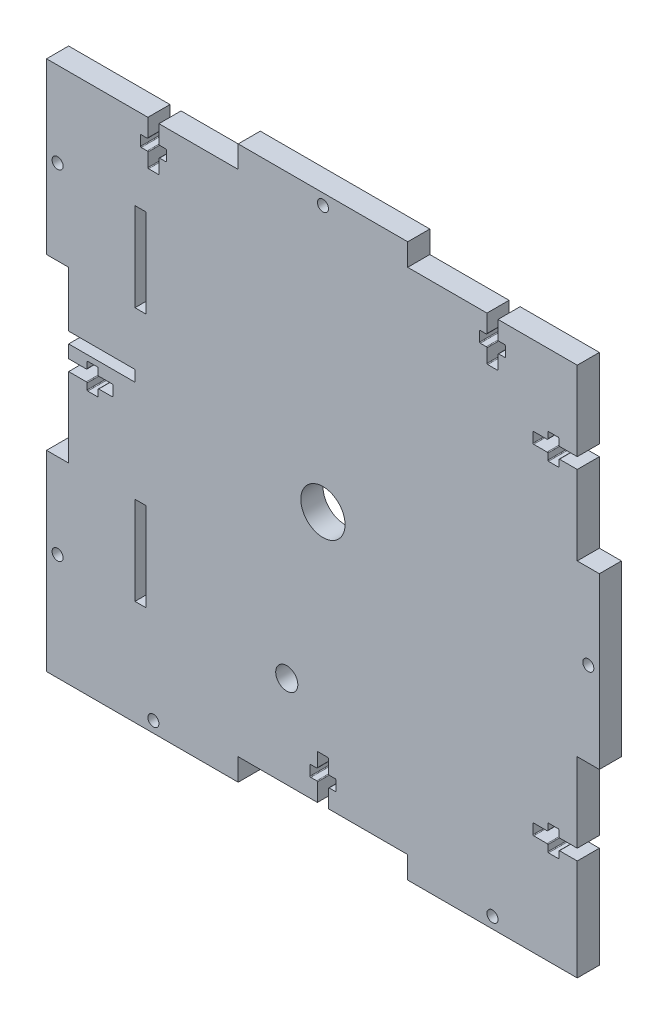
SolidWorks part; units mm, degrees
ref_plane "Front Plane" through (0, 0, 0) normal (0, 0, 1) x (1, 0, 0)
ref_plane "Top Plane" through (0, 0, 0) normal (0, 1, 0) x (1, 0, 0)
ref_plane "Right Plane" through (0, 0, 0) normal (1, 0, 0) x (0, 0, -1)
sketch "Sketch1" plane through (0, 0, 0) normal (0, 0, 1) x (1, 0, 0)
  line L0 (-69, 69) -> (-23, 69)
  line L5 (-75, -75) -> (75, -75) construction
  line L6 (-75, -75) -> (-75, 75) construction
  line L7 (-75, 75) -> (75, 75) construction
  line L8 (75, -75) -> (75, 75) construction
  line L9 (75, 23) -> (69, 23)
  line L10 (69, -23) -> (75, -23)
  line L11 (-69, -69) -> (69, -69) construction
  line L12 (-69, -69) -> (-69, 69) construction
  line L13 (-69, 69) -> (69, 69) construction
  line L14 (69, -69) -> (69, 69) construction
  line L15 (-69, -69) -> (69, 69) construction
  line L16 (69, -69) -> (69, -23)
  line L17 (-23, 69) -> (-23, 75)
  line L18 (-23, 75) -> (23, 75)
  line L19 (23, 75) -> (23, 69)
  line L20 (23, 69) -> (69, 69)
  line L21 (75, -23) -> (75, 23)
  line L22 (69, 23) -> (69, 69)
  line L23 (-75, 23) -> (-69, 23)
  line L24 (-69, 69) -> (-75, 69)
  line L25 (-75, 69) -> (-75, 23)
  line L26 (69, -69) -> (69, -75)
  line L27 (69, -75) -> (23, -75)
  line L28 (23, -75) -> (23, -69)
  line L29 (23, -69) -> (-23, -69)
  line L30 (-23, -69) -> (-23, -75)
  line L31 (-23, -75) -> (-69, -75)
  line L32 (-69, -75) -> (-69, -69) construction
  line L33 (-69, 23) -> (-69, -23)
  line L34 (-69, -23) -> (-75, -23)
  line L35 (-75, -23) -> (-75, -69)
  line L36 (-75, -69) -> (-69, -69) construction
  line L37 (-46, 69) -> (-46, -75) construction
  line L38 (-69, 69) -> (69, -69) construction
  line L39 (-75, -75) -> (-69, -75)
  line L40 (-75, -75) -> (-75, -69)
  point P0 (0, 0)
  point P6 (-7, -7)
  point P26 (0, -75)
  point P27 (-75, 0)
  dimension "D1" = 150
  dimension "D2" = 150
  dimension "D5" = 46
  dimension "D3" = 6
  dimension "D6" = 6
  dimension "D7" = 6
extrude "Box Side" add sketch "Sketch1" along normal blind 6
sketch "Sketch2" plane through (0, 0, 6) normal (0, 0, 1) x (1, 0, 0)
  line L0 (23, 72) -> (-23, 72) construction
  line L1 (23, 75) -> (23, 69) construction
  line L2 (-23, 69) -> (-23, 75) construction
  line L3 (-46, 69) -> (-46, -75) construction
  line L5 (0, 75) -> (0, 69) construction
  line L6 (-23, 75) -> (23, 75) construction
  line L7 (-69, 69) -> (69, 69) construction
  line L16 (-46, 69) -> (-46, -75) construction
  line L21 (0, -69) -> (0, 69) construction
  line L35 (-69, 69) -> (-23, 69) construction
  line L36 (-44.5, 69) -> (-44.5, 64.2)
  line L37 (-44.3, 64) -> (-42.7, 64)
  line L38 (-42.5, 63.8) -> (-42.5, 61.2)
  line L39 (-42.7, 61) -> (-44.3, 61)
  line L40 (-44.5, 60.8) -> (-44.5, 57.2)
  line L46 (-44.7, 57) -> (-47.3, 57)
  line L48 (-44.5, 69) -> (-47.5, 69)
  line L51 (-47.5, 60.8) -> (-47.5, 57.2)
  line L52 (-49.3, 61) -> (-47.7, 61)
  line L53 (-49.5, 63.8) -> (-49.5, 61.2)
  line L54 (-47.7, 64) -> (-49.3, 64)
  line L55 (-47.5, 69) -> (-47.5, 64.2)
  line L56 (47.5, 69) -> (47.5, 64.2)
  line L57 (47.7, 64) -> (49.3, 64)
  line L58 (49.5, 63.8) -> (49.5, 61.2)
  line L59 (49.3, 61) -> (47.7, 61)
  line L60 (47.5, 60.8) -> (47.5, 57.2)
  line L61 (44.5, 69) -> (47.5, 69)
  line L62 (44.7, 57) -> (47.3, 57)
  line L63 (44.5, 60.8) -> (44.5, 57.2)
  line L64 (42.7, 61) -> (44.3, 61)
  line L65 (42.5, 63.8) -> (42.5, 61.2)
  line L66 (44.3, 64) -> (42.7, 64)
  line L67 (44.5, 69) -> (44.5, 64.2)
  line L68 (-69, -69) -> (69, 69) construction
  line L69 (-69, -69) -> (69, 69) construction
  line L70 (75, 0) -> (69, 0) construction
  line L71 (72, 23) -> (72, -23) construction
  line L72 (69, 44.5) -> (64.2, 44.5)
  line L73 (64, 44.3) -> (64, 42.7)
  line L74 (63.8, 42.5) -> (61.2, 42.5)
  line L75 (61, 42.7) -> (61, 44.3)
  line L76 (60.8, 44.5) -> (57.2, 44.5)
  line L77 (57, 44.7) -> (57, 47.3)
  line L78 (69, 44.5) -> (69, 47.5)
  line L79 (60.8, 47.5) -> (57.2, 47.5)
  line L80 (61, 49.3) -> (61, 47.7)
  line L81 (63.8, 49.5) -> (61.2, 49.5)
  line L82 (64, 47.7) -> (64, 49.3)
  line L83 (69, 47.5) -> (64.2, 47.5)
  line L84 (69, -47.5) -> (64.2, -47.5)
  line L85 (64, -47.7) -> (64, -49.3)
  line L86 (63.8, -49.5) -> (61.2, -49.5)
  line L87 (61, -49.3) -> (61, -47.7)
  line L88 (60.8, -47.5) -> (57.2, -47.5)
  line L89 (69, -44.5) -> (69, -47.5)
  line L90 (57, -44.7) -> (57, -47.3)
  line L91 (60.8, -44.5) -> (57.2, -44.5)
  line L92 (61, -42.7) -> (61, -44.3)
  line L93 (63.8, -42.5) -> (61.2, -42.5)
  line L94 (64, -44.3) -> (64, -42.7)
  line L95 (69, -44.5) -> (64.2, -44.5)
  line L120 (-69, 69) -> (69, -69) construction
  line L121 (-69, 69) -> (69, -69) construction
  line L122 (-1.5, -69) -> (1.5, -69)
  line L123 (-23, -69) -> (23, -69) construction
  line L124 (1.5, -69) -> (1.5, -64.2)
  line L125 (1.7, -64) -> (3.3, -64)
  line L126 (3.5, -63.8) -> (3.5, -61.2)
  line L127 (3.3, -61) -> (1.7, -61)
  line L128 (1.5, -60.8) -> (1.5, -57.2)
  line L129 (1.3, -57) -> (-1.3, -57)
  line L130 (-1.5, -60.8) -> (-1.5, -57.2)
  line L131 (-3.3, -61) -> (-1.7, -61)
  line L132 (-3.5, -63.8) -> (-3.5, -61.2)
  line L133 (-1.7, -64) -> (-3.3, -64)
  line L134 (-1.5, -69) -> (-1.5, -64.2)
  line L135 (-69, -1.5) -> (-64.2, -1.5)
  line L136 (-64, -1.7) -> (-64, -3.3)
  line L137 (-63.8, -3.5) -> (-61.2, -3.5)
  line L138 (-61, -3.3) -> (-61, -1.7)
  line L139 (-60.8, -1.5) -> (-57.2, -1.5)
  line L140 (-57, 1.3) -> (-57, -1.3)
  line L141 (-60.8, 1.5) -> (-57.2, 1.5)
  line L142 (-61, 3.3) -> (-61, 1.7)
  line L143 (-63.8, 3.5) -> (-61.2, 3.5)
  line L144 (-64, 1.7) -> (-64, 3.3)
  line L145 (-69, 1.5) -> (-64.2, 1.5)
  line L146 (-69, -1.5) -> (-69, 1.5)
  line L147 (-69, -72) -> (-23, -72) construction
  line L148 (-23, 69) -> (-75, 69) construction
  line L149 (-23, -75) -> (-23, -69) construction
  line L150 (-69, -69) -> (-69, -75) construction
  line L151 (-75, -75) -> (-23, -75) construction
  circle A0 centre (0, 72) radius 1.5
  arc A1 (-44.5, 57.2) -> (-44.7, 57) centre (-44.7, 57.2) cw
  arc A2 (-44.3, 61) -> (-44.5, 60.8) centre (-44.3, 60.8) ccw
  arc A3 (-42.5, 61.2) -> (-42.7, 61) centre (-42.7, 61.2) cw
  arc A4 (-42.7, 64) -> (-42.5, 63.8) centre (-42.7, 63.8) cw
  arc A5 (-44.5, 64.2) -> (-44.3, 64) centre (-44.3, 64.2) ccw
  arc A6 (-47.5, 64.2) -> (-47.7, 64) centre (-47.7, 64.2) cw
  arc A7 (-49.3, 64) -> (-49.5, 63.8) centre (-49.3, 63.8) ccw
  arc A8 (-49.5, 61.2) -> (-49.3, 61) centre (-49.3, 61.2) ccw
  arc A9 (-47.7, 61) -> (-47.5, 60.8) centre (-47.7, 60.8) cw
  arc A10 (-47.5, 57.2) -> (-47.3, 57) centre (-47.3, 57.2) ccw
  arc A11 (47.5, 57.2) -> (47.3, 57) centre (47.3, 57.2) cw
  arc A12 (47.7, 61) -> (47.5, 60.8) centre (47.7, 60.8) ccw
  arc A13 (49.5, 61.2) -> (49.3, 61) centre (49.3, 61.2) cw
  arc A14 (49.3, 64) -> (49.5, 63.8) centre (49.3, 63.8) cw
  arc A15 (47.5, 64.2) -> (47.7, 64) centre (47.7, 64.2) ccw
  arc A16 (44.5, 64.2) -> (44.3, 64) centre (44.3, 64.2) cw
  arc A17 (42.7, 64) -> (42.5, 63.8) centre (42.7, 63.8) ccw
  arc A18 (42.5, 61.2) -> (42.7, 61) centre (42.7, 61.2) ccw
  arc A19 (44.3, 61) -> (44.5, 60.8) centre (44.3, 60.8) cw
  arc A20 (44.5, 57.2) -> (44.7, 57) centre (44.7, 57.2) ccw
  arc A21 (57.2, 44.5) -> (57, 44.7) centre (57.2, 44.7) cw
  arc A22 (61, 44.3) -> (60.8, 44.5) centre (60.8, 44.3) ccw
  arc A23 (61.2, 42.5) -> (61, 42.7) centre (61.2, 42.7) cw
  arc A24 (64, 42.7) -> (63.8, 42.5) centre (63.8, 42.7) cw
  arc A25 (64.2, 44.5) -> (64, 44.3) centre (64.2, 44.3) ccw
  arc A26 (64.2, 47.5) -> (64, 47.7) centre (64.2, 47.7) cw
  arc A27 (64, 49.3) -> (63.8, 49.5) centre (63.8, 49.3) ccw
  arc A28 (61.2, 49.5) -> (61, 49.3) centre (61.2, 49.3) ccw
  arc A29 (61, 47.7) -> (60.8, 47.5) centre (60.8, 47.7) cw
  arc A30 (57.2, 47.5) -> (57, 47.3) centre (57.2, 47.3) ccw
  arc A31 (57.2, -47.5) -> (57, -47.3) centre (57.2, -47.3) cw
  arc A32 (61, -47.7) -> (60.8, -47.5) centre (60.8, -47.7) ccw
  arc A33 (61.2, -49.5) -> (61, -49.3) centre (61.2, -49.3) cw
  arc A34 (64, -49.3) -> (63.8, -49.5) centre (63.8, -49.3) cw
  arc A35 (64.2, -47.5) -> (64, -47.7) centre (64.2, -47.7) ccw
  arc A36 (64.2, -44.5) -> (64, -44.3) centre (64.2, -44.3) cw
  arc A37 (64, -42.7) -> (63.8, -42.5) centre (63.8, -42.7) ccw
  arc A38 (61.2, -42.5) -> (61, -42.7) centre (61.2, -42.7) ccw
  arc A39 (61, -44.3) -> (60.8, -44.5) centre (60.8, -44.3) cw
  arc A40 (57.2, -44.5) -> (57, -44.7) centre (57.2, -44.7) ccw
  circle A41 centre (72, 0) radius 1.5
  arc A62 (1.5, -57.2) -> (1.3, -57) centre (1.3, -57.2) ccw
  arc A63 (1.7, -61) -> (1.5, -60.8) centre (1.7, -60.8) cw
  arc A64 (3.5, -61.2) -> (3.3, -61) centre (3.3, -61.2) ccw
  arc A65 (3.3, -64) -> (3.5, -63.8) centre (3.3, -63.8) ccw
  arc A66 (1.5, -64.2) -> (1.7, -64) centre (1.7, -64.2) cw
  arc A67 (-1.5, -64.2) -> (-1.7, -64) centre (-1.7, -64.2) ccw
  arc A68 (-3.3, -64) -> (-3.5, -63.8) centre (-3.3, -63.8) cw
  arc A69 (-3.5, -61.2) -> (-3.3, -61) centre (-3.3, -61.2) cw
  arc A70 (-1.7, -61) -> (-1.5, -60.8) centre (-1.7, -60.8) ccw
  arc A71 (-1.5, -57.2) -> (-1.3, -57) centre (-1.3, -57.2) cw
  arc A72 (-57.2, -1.5) -> (-57, -1.3) centre (-57.2, -1.3) ccw
  arc A73 (-61, -1.7) -> (-60.8, -1.5) centre (-60.8, -1.7) cw
  arc A74 (-61.2, -3.5) -> (-61, -3.3) centre (-61.2, -3.3) ccw
  arc A75 (-64, -3.3) -> (-63.8, -3.5) centre (-63.8, -3.3) ccw
  arc A76 (-64.2, -1.5) -> (-64, -1.7) centre (-64.2, -1.7) cw
  arc A77 (-64.2, 1.5) -> (-64, 1.7) centre (-64.2, 1.7) ccw
  arc A78 (-64, 3.3) -> (-63.8, 3.5) centre (-63.8, 3.3) cw
  arc A79 (-61.2, 3.5) -> (-61, 3.3) centre (-61.2, 3.3) cw
  arc A80 (-61, 1.7) -> (-60.8, 1.5) centre (-60.8, 1.7) ccw
  arc A81 (-57.2, 1.5) -> (-57, 1.3) centre (-57.2, 1.3) cw
  circle A82 centre (-46, -72) radius 1.5
  circle A83 centre (46, -72) radius 1.5
  circle A84 centre (-72, 46) radius 1.5
  circle A85 centre (-72, -46) radius 1.5
  point P6 (0, 72)
  point P38 (0, 0)
  point P56 (-46, 57)
  point P88 (46, 57)
  point P161 (57, 46)
  point P162 (57, -46)
  point P198 (0, -57)
  point P231 (-57, 0)
  point P234 (-42.5, 62.5)
  dimension "D1" = 3
  dimension "D2" = 0.2
  dimension "D8" = 0.2
  dimension "D14" = 3
  dimension "D4" = 3
  dimension "D7" = 1.5
  dimension "D10" = 3
  dimension "D12" = 1.5
  dimension "D9" = 12
  dimension "D11" = 5
  dimension "D13" = 7
  dimension "D3" = 12
  dimension "D5" = 7
  dimension "D6" = 5
extrude "Screw Cut-outs" cut sketch "Sketch2" against normal through all
sketch "Sketch3" plane through (0, 0, 6) normal (0, 0, 1) x (1, 0, 0)
  line L0 (-69, -69) -> (69, 69) construction
  line L1 (-69, -69) -> (69, 69) construction
  line L2 (-69, 69) -> (69, -69) construction
  line L3 (-69, 69) -> (69, -69) construction
  circle A0 centre (0, 0) radius 6
  point P4 (0, 0)
  dimension "D1" = 12
extrude "BearingHole" cut sketch "Sketch3" against normal through all
sketch "Sketch4" plane through (0, 0, 6) normal (0, 0, 1) x (1, 0, 0)
  line L0 (-69, 23) -> (-69, 1.5) construction
  line L1 (-69, 5) -> (-51, 5)
  line L2 (-69, 5) -> (-69, 8)
  line L3 (-69, 8) -> (-51, 8)
  line L4 (-51, 5) -> (-51, 8)
  line L5 (-61.2, 3.5) -> (-63.8, 3.5) construction
  line L6 (-75, -23) -> (-75, -75) construction
  line L7 (-51, 46.5) -> (-48, 46.5)
  line L8 (-51, 46.5) -> (-51, 22.5)
  line L9 (-51, 22.5) -> (-48, 22.5)
  line L10 (-48, 46.5) -> (-48, 22.5)
  line L11 (-51, -22.5) -> (-48, -22.5)
  line L12 (-51, -22.5) -> (-51, -46.5)
  line L13 (-51, -46.5) -> (-48, -46.5)
  line L14 (-48, -22.5) -> (-48, -46.5)
  line L15 (-47.5, 69) -> (-75, 69) construction
  dimension "D1" = 3
  dimension "D2" = 1.5
  dimension "D3" = 18
  dimension "D4" = 3
  dimension "D5" = 24
  dimension "D6" = 24
  dimension "D7" = 22.5
  dimension "D8" = 45
extrude "Grooves" cut sketch "Sketch4" against normal up to surface (6 mm away) up to face at (6, 0, 0)
sketch "Sketch5" plane through (0, 0, 6) normal (0, 0, 1) x (1, 0, 0)
  line L0 (1.5, -69) -> (23, -69) construction
  line L3 (-75, -23) -> (-75, -75) construction
  circle A0 centre (-9.82, -44) radius 3
  dimension "D1" = 6
  dimension "D3" = 65.18
  dimension "D2" = 25
extrude "clockwiseShaftHole" cut sketch "Sketch5" against normal through all
equation "\"filletRadius\"=0.2"
equation "\"D8@Sketch2\"=\"filletRadius\""
equation "\"D2@Sketch2\"=\"filletRadius\""
equation "\"fingerWidth\"= 46"
equation "\"D5@Sketch1\"=\"fingerWidth\""
equation "\"wallThickness\"= 6"
equation "\"D3@Sketch1\" = \"wallThickness\""
equation "\"D6@Sketch1\" = \"wallThickness\""
equation "\"D7@Sketch1\" = \"wallThickness\""
equation "\"D1@Box Side\" = \"wallThickness\""
equation "\"M3\"= 3"
equation "\"D14@Sketch2\"=\"M3\""
equation "\"D1@Sketch2\"=\"M3\""
equation "\"D12@Sketch2\"=\"M3\"/2"
equation "\"nutThickness\"=3"
equation "\"D10@Sketch2\" = \"nutThickness\""
equation "\"boltLength\"= 12"
equation "\"D9@Sketch2\" = \"boltLength\""
equation "\"distanceToNut\"= 5"
equation "\"D11@Sketch2\" = \"distanceToNut\""
equation "\"D13@Sketch2\" = \"nutWidth\""
equation "\"D7@Sketch2\"=\"M3\"/2"
equation "\"D4@Sketch2\" = \"nutThickness\""
equation "\"D3@Sketch2\" = \"boltLength\""
equation "\"D5@Sketch2\" = \"nutWidth\""
equation "\"D6@Sketch2\" = \"distanceToNut\""
equation "\"sideLength\"=150"
equation "\"D1@Sketch1\"=\"sideLength\""
equation "\"D2@Sketch1\"=\"sideLength\""
equation "\"nutWidth\"=7"
